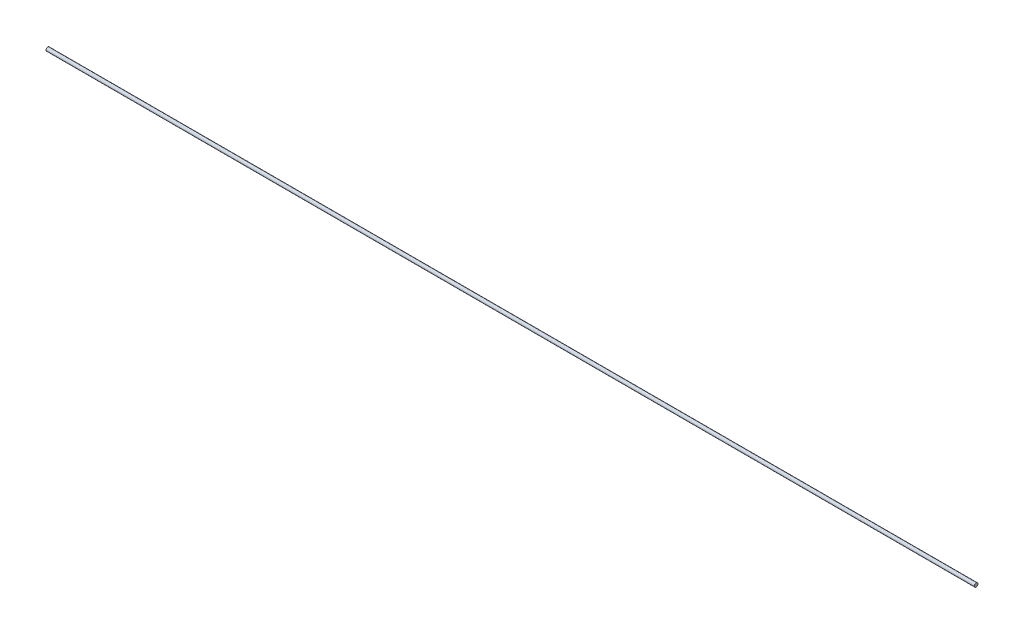
SolidWorks part; units mm, degrees
material "AISI 1020"
ref_plane "Front Plane" through (0, 0, 0) normal (0, 0, 1) x (1, 0, 0)
ref_plane "Top Plane" through (0, 0, 0) normal (0, 1, 0) x (1, 0, 0)
ref_plane "Right Plane" through (0, 0, 0) normal (1, 0, 0) x (0, 0, -1)
sketch "Sketch1" plane through (0, 0, 0) normal (1, 0, 0) x (0, 0, -1)
  circle A0 centre (0, 0) radius 3.175
  dimension "D1" = 6.35
extrude "Boss-Extrude1" add sketch "Sketch1" along normal blind 1651
equation "\"OD\"= 1 / 4"
equation "\"L\"= 65"
equation "\"D1@Sketch1\"=\"OD\""
equation "\"D1@Boss-Extrude1\"=\"L\""
